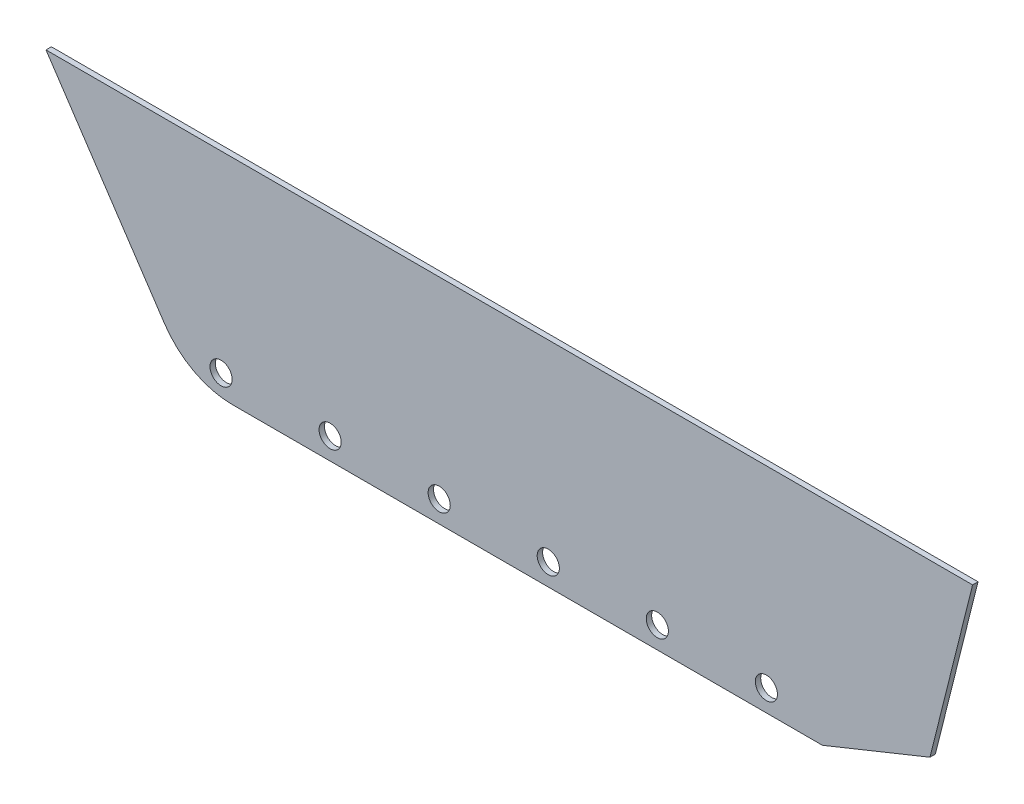
SolidWorks part; units mm, degrees
material "5052-H34"
ref_plane "Front Plane" through (0, 0, 0) normal (0, 0, 1) x (1, 0, 0)
ref_plane "Top Plane" through (0, 0, 0) normal (0, 1, 0) x (1, 0, 0)
ref_plane "Right Plane" through (0, 0, 0) normal (1, 0, 0) x (0, 0, -1)
sketch "Sketch1" plane through (0, 0, 0) normal (0, 0, 1) x (1, 0, 0)
  line L6 (-98.8794, 3.851) -> (-31.8794, -96.649)
  line L7 (428.1206, 28.9396) -> (403.1206, -71.149)
  line L9 (403.1206, -71.149) -> (366, -96.649)
  line L10 (-31.8794, -96.649) -> (366, -96.649)
  line L12 (-98.8794, 3.851) -> (-115.6052, 28.9396)
  line L13 (-115.6052, 28.9396) -> (428.1206, 28.9396)
  circle A0 centre (-12.8794, -83.899) radius 6.5
  circle A1 centre (51.1206, -83.899) radius 6.5
  circle A2 centre (115.1206, -83.899) radius 6.5
  circle A3 centre (179.1206, -83.899) radius 6.5
  circle A4 centre (243.1206, -83.899) radius 6.5
  circle A5 centre (307.1206, -83.899) radius 6.5
  point P0 (-48.8794, -71.149)
  point P1 (-132.601, -47.6495)
  point P2 (-31.8794, -96.649)
  point P5 (0, 0)
  point P8 (48, -83.899)
  point P9 (403.1206, -71.149)
  dimension "D2" = 64
  dimension "D4" = 64
  dimension "D15" = 13
  dimension "D1" = 25.5
  dimension "D3" = 75
  dimension "D5" = 25
  dimension "D6" = 96
  dimension "D7" = 527
  dimension "D8" = 180
  dimension "D9" = 64
  dimension "D10" = 64
  dimension "D11" = 64
  dimension "D12" = 123.69
  dimension "D13" = 12.75
  dimension "D14" = 543.7258
  dimension "D16" = 366
extrude "Boss-Extrude1" add sketch "Sketch1" along normal blind 3.175 contours L12 L13 L7 L9 L10 L6
extrude "Cut-Extrude1" cut sketch "Sketch1<4>" along normal through all contours A0 | A1 | A2 | A3 | A4 | A5 region at (-12.8794, -83.899, 0)
sketch "Sketch1<4>" plane through (0, 0, 0) normal (0, 0, 1) x (1, 0, 0) same geometry as "Sketch1"
sketch "Sketch2" plane through (0, 0, 0) normal (0, 0, -1) x (-1, 0, 0)
  circle A0 centre (-275.1206, -83.899) radius 6.5
  circle A2 centre (-233.5603, -132.5687) radius 6.5
  circle A3 centre (-192, -83.899) radius 6.5
  circle A4 centre (-128, -83.899) radius 6.5
  circle A5 centre (-64, -83.899) radius 6.5
  circle A6 centre (0, -83.899) radius 6.5
  dimension "D2" = 0
  dimension "D3" = 64
  dimension "D4" = 64
  dimension "D5" = 64
  dimension "D6" = 64
  dimension "D7" = 64
  dimension "D1" = 32
sketch "Sketch5" plane through (0, 0, 0) normal (0, 0, -1) x (-1, 0, 0)
  line L0 (48.8794, -71.149) -> (-14.2353, -96.649)
  line L1 (31.8794, -96.649) -> (-366, -96.649) construction
  line L2 (-14.2353, -96.649) -> (31.8794, -96.649)
  line L3 (31.8794, -96.649) -> (48.8794, -71.149)
  line L6 (-366, -96.649) -> (-403.1206, -71.149)
  line L7 (-403.1206, -71.149) -> (-352, -71.149)
  line L9 (-352, -71.149) -> (-326.5, -96.649)
  line L11 (-366, -96.649) -> (-326.5, -96.649)
  dimension "D1" = 22
  dimension "D2" = 45
extrude "Cut-Extrude2" [suppressed] cut sketch "Sketch5" against normal up to next
sketch "Sketch6" plane through (0, 0, 3.175) normal (0, 0, 1) x (1, 0, 0)
  line L0 (-48.8794, -71.149) -> (14.2353, -96.649)
  line L1 (-31.8794, -96.649) -> (366, -96.649) construction
  line L2 (14.2353, -96.649) -> (-31.8794, -96.649)
  line L3 (-31.8794, -96.649) -> (-48.8794, -71.149)
  dimension "D1" = 158
fillet "Fillet1" radius 48 1 edges at (-31.8794, -96.649, 1.5875)
sketch "Sketch7" plane through (0, 0, 3.175) normal (0, 0, 1) x (1, 0, 0)
  line L0 (403.1206, -71.149) -> (340.0059, -96.649)
  line L1 (-31.8794, -96.649) -> (366, -96.649) construction
  line L2 (340.0059, -96.649) -> (366, -96.649)
  line L3 (366, -96.649) -> (403.1206, -71.149)
  dimension "D1" = 22
extrude "Cut-Extrude3" cut sketch "Sketch7" against normal blind 10
sketch "Sketch9" plane through (0, 0, 0) normal (0, 0, -1) x (-1, 0, 0)
  line L0 (-403.1206, -71.149) -> (48.8794, -71.149)
  line L1 (48.8794, -71.149) -> (48.8794, -114.9143)
  line L2 (48.8794, -114.9143) -> (-403.1206, -114.9143)
  line L3 (-403.1206, -114.9143) -> (-403.1206, -71.149)
extrude "Cut-Extrude4" [suppressed] cut sketch "Sketch9" against normal blind 10
